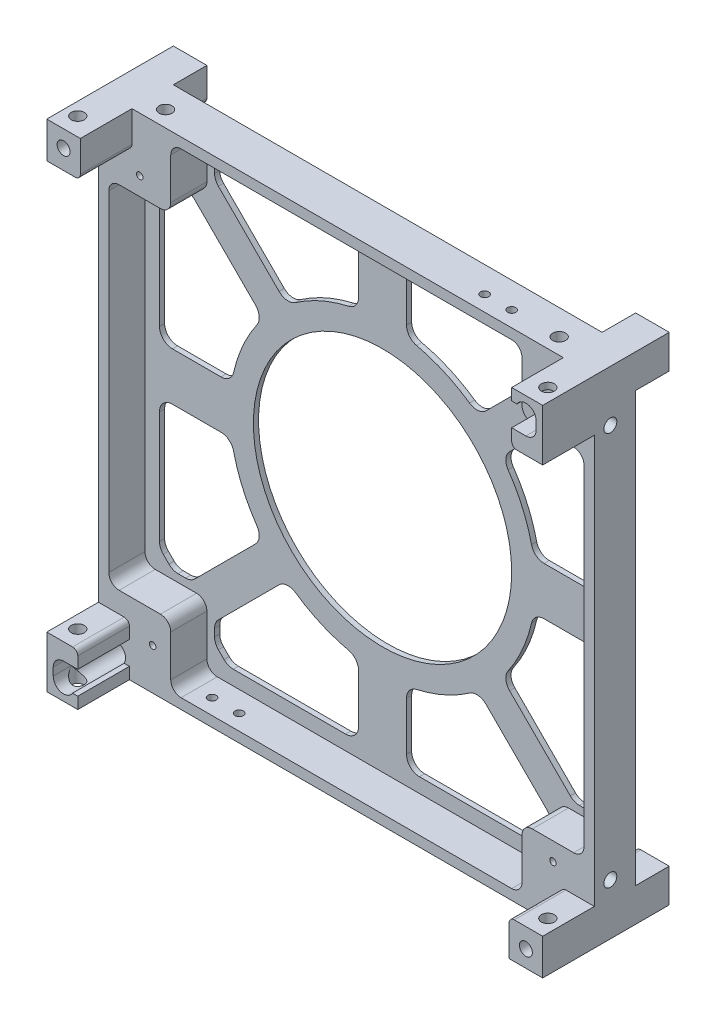
SolidWorks part; units mm, degrees
other "Markup1"
sketch "Sketch35" plane through (-48, 48, 17) normal (-0.4622, 0.8807, 0.1038) x (-0.8777, -0.471, 0.0879)
material "7075-T6 (SN)"
ref_plane "Front Plane" through (0, 0, 0) normal (0, 0, 1) x (1, 0, 0)
ref_plane "Top Plane" through (0, 0, 0) normal (0, 1, 0) x (1, 0, 0)
ref_plane "Right Plane" through (0, 0, 0) normal (1, 0, 0) x (0, 0, -1)
sketch "Sketch1" plane through (0, 0, 0) normal (0, 0, 1) x (1, 0, 0)
  line L0 (0, 0) -> (0, 62.6225) construction
  line L1 (-48, 48) -> (48, 48) construction
  line L2 (-48, 48) -> (-48, -48) construction
  line L3 (-48, -48) -> (48, -48) construction
  line L4 (48, 48) -> (48, -48) construction
  line L5 (0, 0) -> (75.6556, 0) construction
  point P4 (0, 48)
  point P5 (-48, 0)
  dimension "D1" = 96
  dimension "D2" = 96
sketch "Sketch2" plane through (0, 0, 0) normal (0, 0, 1) x (1, 0, 0)
  line L1 (48, 48) -> (41.5, 48)
  line L2 (48, 48) -> (48, 41.5)
  line L3 (48, 41.5) -> (41.5, 41.5)
  line L4 (41.5, 48) -> (41.5, 41.5)
  line L5 (48, -48) -> (41.5, -48)
  line L6 (48, -48) -> (48, -41.5)
  line L7 (48, -41.5) -> (41.5, -41.5)
  line L8 (41.5, -48) -> (41.5, -41.5)
  line L9 (-48, -48) -> (-41.5, -48)
  line L10 (-48, -48) -> (-48, -41.5)
  line L11 (-48, -41.5) -> (-41.5, -41.5)
  line L12 (-41.5, -48) -> (-41.5, -41.5)
  line L13 (-48, 48) -> (-41.5, 48)
  line L14 (-48, 48) -> (-48, 41.5)
  line L15 (-48, 41.5) -> (-41.5, 41.5)
  line L16 (-41.5, 48) -> (-41.5, 41.5)
  dimension "D1" = 6.5
  dimension "D2" = 6.5
  dimension "D3" = 6.5
  dimension "D4" = 6.5
  dimension "D5" = 6.5
  dimension "D6" = 6.5
  dimension "D7" = 6.5
  dimension "D8" = 6.5
sketch "Sketch3" plane through (0, 0, 0) normal (0, 0, 1) x (1, 0, 0)
  line L0 (48, 48) -> (0, 48)
  line L1 (32.5122, 39.5801) -> (32.5122, 38.1157)
  line L3 (38.1157, 32.5122) -> (39.5801, 32.5122)
  line L8 (48, 48) -> (48, -48) construction
  line L9 (48, 0) -> (48, 48)
  line L10 (4.64, 40.68) -> (4.64, 31.2753)
  line L12 (0, 0) -> (48, 48) construction
  line L13 (31.78, 41.3479) -> (30.6801, 42.4478)
  line L14 (25, 0) -> (48, 0)
  line L15 (0, -200000) -> (0, 200062.6225) construction
  line L17 (-48, 48) -> (48, 48) construction
  line L21 (0, 25) -> (0, 48)
  line L22 (20.0352, 24.6032) -> (31.78, 36.3479)
  line L23 (24.6032, 20.0352) -> (36.3479, 31.78)
  line L24 (41.3479, 31.78) -> (42.4478, 30.6801)
  line L25 (7.14, 43.18) -> (28.9124, 43.18)
  line L26 (43.18, 7.14) -> (43.18, 28.9124)
  line L27 (40.68, 4.64) -> (31.2753, 4.64)
  arc A0 (25, 0) -> (0, 25) centre (0, 0) ccw
  arc A1 (28.838, 6.5836) -> (24.3158, 16.8439) centre (0, 0) ccw
  arc A2 (16.8439, 24.3158) -> (6.5836, 28.838) centre (0, 0) ccw
  arc A3 (7.14, 43.18) -> (4.64, 40.68) centre (7.14, 40.68) ccw
  arc A4 (4.64, 31.2753) -> (6.5836, 28.838) centre (7.14, 31.2753) ccw
  arc A5 (20.0352, 24.6032) -> (16.8439, 24.3158) centre (18.2675, 26.3709) cw
  arc A7 (28.9124, 43.18) -> (30.6801, 42.4478) centre (28.9124, 40.68) cw
  arc A8 (31.2753, 4.64) -> (28.838, 6.5836) centre (31.2753, 7.14) cw
  arc A9 (40.68, 4.64) -> (43.18, 7.14) centre (40.68, 7.14) ccw
  arc A10 (43.18, 28.9124) -> (42.4478, 30.6801) centre (40.68, 28.9124) ccw
  arc A11 (24.6032, 20.0352) -> (24.3158, 16.8439) centre (26.3709, 18.2675) ccw
  arc A13 (31.78, 41.3479) -> (32.5122, 39.5801) centre (30.0122, 39.5801) cw
  arc A14 (41.3479, 31.78) -> (39.5801, 32.5122) centre (39.5801, 30.0122) ccw
  arc A15 (36.3479, 31.78) -> (38.1157, 32.5122) centre (38.1157, 30.0122) cw
  arc A16 (31.78, 36.3479) -> (32.5122, 38.1157) centre (30.0122, 38.1157) ccw
  point P39 (4.64, 29.2138)
  point P42 (18.5072, 23.0751)
  point P45 (34.28, 38.8479)
  dimension "D1" = 50
  dimension "D2" = 4.58
  dimension "D10" = 2.5
  dimension "D11" = 2.5
  dimension "D12" = 2.5
  dimension "D13" = 2.5
  dimension "D14" = 2.5
  dimension "D3" = 4.64
  dimension "D4" = 4.82
  dimension "D5" = 6.46
  dimension "D6" = 3.23
  dimension "D7" = 4.82
  dimension "D8" = 4.64
  dimension "D9" = 13.72
extrude "Boss-Extrude2" add sketch "Sketch3" along normal blind 1
ref_axis "Axis1" through (0, 0, 7.875) along (0, 0, -1)
pattern_circular "CirPattern3" count 4 over 360 about axis through (0, 0, 7.875) along (0, 0, -1) of "Boss-Extrude2"
extrude "Boss-Extrude3" add sketch "Sketch2" against normal blind 6.5
sketch "Sketch4" plane through (0, 0, 1) normal (0, 0, 1) x (1, 0, 0)
  line L0 (46, -34) -> (46, 34)
  line L1 (34, 46) -> (-34, 46)
  line L2 (-46, 34) -> (-46, -34)
  line L3 (-34, -46) -> (34, -46)
  line L4 (-48, 48) -> (-48, -48)
  line L5 (-48, -48) -> (48, -48)
  line L6 (48, -48) -> (48, 48)
  line L7 (48, 48) -> (-48, 48)
  line L15 (-46, 34) -> (-34, 34)
  line L16 (-34, 46) -> (-34, 34)
  line L19 (46, 34) -> (34, 34)
  line L20 (34, 46) -> (34, 34)
  line L23 (46, -34) -> (34, -34)
  line L24 (34, -46) -> (34, -34)
  line L27 (-46, -34) -> (-34, -34)
  line L28 (-34, -46) -> (-34, -34)
  line L29 (-34, 46) -> (-46, 34) construction
  point P2 (46, -46)
  point P4 (46, 46)
  point P6 (-46, 46)
  point P7 (-46, -46)
  dimension "D3" = 14
  dimension "D4" = 14
  dimension "D5" = 2
  dimension "D6" = 2
  dimension "D1" = 14
  dimension "D2" = 14
  dimension "D7" = 2
  dimension "D8" = 2
extrude "Boss-Extrude4" add sketch "Sketch4" along normal blind 7
sketch "Sketch5" plane through (0, 0, 8) normal (0, 0, 1) x (1, 0, 0)
  line L1 (-48, 48) -> (-41.5, 48)
  line L2 (-48, 48) -> (-48, 41)
  line L3 (-48, 41) -> (-41.5, 41)
  line L4 (-41.5, 48) -> (-41.5, 41)
  line L5 (48, 48) -> (42, 48)
  line L6 (48, 48) -> (48, 38)
  line L7 (48, 38) -> (42, 38)
  line L8 (42, 48) -> (42, 38)
  line L9 (-48, -48) -> (-42, -48)
  line L10 (-48, -48) -> (-48, -38)
  line L11 (-48, -38) -> (-42, -38)
  line L12 (-42, -48) -> (-42, -38)
  line L13 (48, -48) -> (41.5, -48)
  line L14 (48, -48) -> (48, -41)
  line L15 (48, -41) -> (41.5, -41)
  line L16 (41.5, -48) -> (41.5, -41)
  dimension "D1" = 6.5
  dimension "D2" = 7
  dimension "D3" = 6
  dimension "D4" = 10
  dimension "D5" = 6.5
  dimension "D6" = 7
  dimension "D7" = 10
  dimension "D8" = 6
extrude "Boss-Extrude5" add sketch "Sketch5" along normal blind 10
sketch "RailHolePosition" plane through (0, 48, 0) normal (0, 1, 0) x (1, 0, 0)
  line L0 (45.5, 6.5) -> (45.5, -14.5) construction
  line L1 (48, -18) -> (48, 6.5) construction
  line L5 (-45.5, 6.5) -> (-45.5, -14.5) construction
  line L7 (48, 6.5) -> (41.5, 6.5) construction
  line L8 (-48, -18) -> (-48, 6.5) construction
  line L9 (-41.5, 6.5) -> (-48, 6.5) construction
  dimension "D1" = 21
  dimension "D2" = 2.5
  dimension "D3" = 2.5
hole_wizard "M3 Tapped RailHoles" positions "Sketch12" profile "Sketch13" tap size "M3" standard "ISO"
sketch "Sketch12" plane through (0, 48, 0) normal (0, 1, 0) x (1, 0, 0)
  point P8 (45.5, -14.5)
  point P11 (-45.5, -14.5)
sketch "Sketch13" plane through (45.5, 48, 14.5) normal (1, 0, 0) x (0, 0, 1)
  line L0 (0, 0) -> (0, 13.2511)
  line L1 (0, 13.2511) -> (1.25, 12.5)
  line L2 (1.25, 12.5) -> (1.25, 0)
  line L5 (1.25, 0) -> (0, 0)
  line L10 (0, 13.2511) -> (-1.25, 12.5) construction
  line L11 (0, -6.35) -> (0, 107.95) construction
  dimension "Tap Drill Dia." = 2.5
  dimension "Tap Drill Depth" = 12.5
  dimension "Drill Angle" = 118
cosmetic thread "Hole Thread1" parameters "D1"=7, "D2"=3
cosmetic thread "Hole Thread19" parameters "D1"=7, "D2"=3
sketch3d "SidePlateHole Positions"
  line L0 (-38.1, -48, 8) -> (-38.1, -48, 0) construction
  line L1 (-42, -48, 8) -> (41.5, -48, 8) construction
  line L2 (-48, -48, 0) -> (48, -48, 0) construction
  line L3 (-38.1, -48, 4.9) -> (-48, -48, 4.9) construction
  line L5 (-48, -48, 18) -> (-48, -48, -6.5) construction
  line L6 (-41.5, -48, 0) -> (41.5, -48, 0) construction
  line L17 (-48, -48, 4.9) -> (-48, -38.1, 4.9) construction
  line L18 (-48, -38.1, 4.9) -> (-48, -38.1, 0) construction
  line L19 (-48, 48, 0) -> (-48, -48, 0) construction
  dimension "D1" = 4.9
  dimension "D2" = 9.9
  dimension "D7" = 9.9
hole_wizard "M3x0.5 Tapped SidePlate" positions "Sketch16" profile "Sketch17" tap size "M3x0.5" standard "ANSI Metric"
sketch "Sketch16" plane through (0, -48, 0) normal (0, -1, 0) x (-1, 0, 0)
  point P0 (38.1, -4.9)
sketch "Sketch17" plane through (-38.1, -48, 4.9) normal (1, 0, 0) x (0, 0, -1)
  line L0 (0, 0) -> (0, 8.2511)
  line L1 (0, 8.2511) -> (1.25, 7.5)
  line L2 (1.25, 7.5) -> (1.25, 0)
  line L5 (1.25, 0) -> (0, 0)
  line L10 (0, 8.2511) -> (-1.25, 7.5) construction
  line L11 (0, -6.35) -> (0, 107.95) construction
  dimension "Tap Drill Dia." = 2.5
  dimension "Tap Drill Depth" = 7.5
  dimension "Drill Angle" = 118
cosmetic thread "Hole Thread3" parameters "D1"=6, "D2"=3
hole_wizard "M3x0.5 Tapped SidePlate2" positions "Sketch18" profile "Sketch19" tap size "M3x0.5" standard "ANSI Metric"
sketch "Sketch18" plane through (-48, 0, 0) normal (-1, 0, 0) x (0, 0, 1)
  point P0 (4.9, -38.1)
sketch "Sketch19" plane through (-48, -38.1, 4.9) normal (0, 1, 0) x (0, 0, 1)
  line L0 (0, 0) -> (0, 8.2511)
  line L1 (0, 8.2511) -> (1.25, 7.5)
  line L2 (1.25, 7.5) -> (1.25, 0)
  line L5 (1.25, 0) -> (0, 0)
  line L10 (0, 8.2511) -> (-1.25, 7.5) construction
  line L11 (0, -6.35) -> (0, 107.95) construction
  dimension "Tap Drill Dia." = 2.5
  dimension "Tap Drill Depth" = 7.5
  dimension "Drill Angle" = 118
cosmetic thread "Hole Thread4" parameters "D1"=6, "D2"=3
pattern_circular "SidePlateHoles" count 4 over 360 about axis through (0, 0, 1) along (0, 0, -1) of "M3x0.5 Tapped SidePlate", "M3x0.5 Tapped SidePlate2"
cosmetic thread "Hole Thread5" parameters "D1"=6, "D2"=3
cosmetic thread "Hole Thread6" parameters "D1"=6, "D2"=3
cosmetic thread "Hole Thread7" parameters "D1"=6, "D2"=3
cosmetic thread "Hole Thread8" parameters "D1"=6, "D2"=3
cosmetic thread "Hole Thread9" parameters "D1"=6, "D2"=3
cosmetic thread "Hole Thread10" parameters "D1"=6, "D2"=3
sketch3d "LimitSwitchHolePositions"
  line L0 (-48, -48, 5) -> (-29, -48, 5) construction
  line L1 (-48, -48, 18) -> (-48, -48, -6.5) construction
  line L2 (-48, -48, 0) -> (48, -48, 0) construction
  line L3 (-29, -48, 5) -> (-23.75, -48, 5) construction
  dimension "D1" = 19
  dimension "D2" = 5
  dimension "D3" = 5.25
hole_wizard "M2x0.4 Tapped Hole1" positions "Sketch20" profile "Sketch21" tap size "M2x0.4" standard "ANSI Metric"
sketch "Sketch20" plane through (0, -48, 0) normal (0, -1, 0) x (-1, 0, 0)
  point P0 (29, -5)
  point P3 (23.75, -5)
sketch "Sketch21" plane through (-29, -48, 5) normal (1, 0, 0) x (0, 0, -1)
  line L0 (0, 0) -> (0, 5.6807)
  line L1 (0, 5.6807) -> (0.8, 5.2)
  line L2 (0.8, 5.2) -> (0.8, 0)
  line L5 (0.8, 0) -> (0, 0)
  line L10 (0, 5.6807) -> (-0.8, 5.2) construction
  line L11 (0, -6.35) -> (0, 107.95) construction
  dimension "Tap Drill Dia." = 1.6
  dimension "Tap Drill Depth" = 5.2
  dimension "Drill Angle" = 118
cosmetic thread "Hole Thread11" parameters "D1"=4, "D2"=2
cosmetic thread "Hole Thread12" parameters "D1"=4, "D2"=2
pattern_circular "LimitSwitchHoles" count 2 over 360 about axis through (0, 0, 1) along (0, 0, -1) of "M2x0.4 Tapped Hole1"
cosmetic thread "Hole Thread13" parameters "D1"=4, "D2"=2
cosmetic thread "Hole Thread14" parameters "D1"=4, "D2"=2
fillet "Fillet2" radius 2 12 edges at (-46, -34, 4.5) (-34, -34, 4.5) (-34, -46, 4.5) (34, -46, 4.5) (34, -34, 4.5) (46, -34, 4.5) (46, 34, 4.5) (34, 34, 4.5) (34, 46, 4.5) (-34, 46, 4.5) (-34, 34, 4.5) (-46, 34, 4.5)
sketch "Sketch22" plane through (0, 0, 18) normal (0, 0, 1) x (1, 0, 0)
  line L0 (44.75, 48) -> (44.75, 44.75) construction
  line L1 (48, 48) -> (42, 48) construction
  line L3 (48, 38) -> (48, 48) construction
  dimension "D1" = 3.25
  dimension "D2" = 3.25
hole_wizard "M3 Tapped Standoff Hole" positions "Sketch23" profile "Sketch25" tap size "M3" standard "ISO" end condition through all
sketch "Sketch23" plane through (0, 0, 18) normal (0, 0, 1) x (1, 0, 0)
  point P0 (-44.75, 44.75)
sketch "Sketch25" plane through (-44.75, 44.75, 18) normal (1, 0, 0) x (0, -1, 0)
  line L0 (0, 0) -> (0, 24.5)
  line L1 (0, 24.5) -> (1.25, 24.5)
  line L2 (1.25, 24.5) -> (1.25, 0)
  line L5 (1.25, 0) -> (0, 0)
  line L11 (0, -6.35) -> (0, 107.95) construction
  dimension "Thread Major Dia." = 2.5
  dimension "Thru Tap Drill Depth" = 24.5
pattern_circular "StandoffHoles" count 2 over 360 about axis through (0, 0, 1) along (0, 0, -1) of "M3 Tapped Standoff Hole"
sketch "Sketch26" plane through (0, 0, 0) normal (0, 0, -1) x (-1, 0, 0)
  line L0 (0, 0) -> (37.5, -40) construction
  line L1 (0, -200000) -> (0, 200062.6225) construction
  line L2 (200000, 0) -> (-200075.6556, 0) construction
  line L3 (13.475, 0) -> (-13.475, 0) construction
  line L4 (0, 0) -> (37.5, 40) construction
  circle A0 centre (37.5, -40) radius 1.7
  dimension "D3" = 3.4
  dimension "D1" = 37.5
  dimension "D2" = 40
extrude "Boss-Extrude6" add sketch "Sketch26" along normal blind 3
hole_wizard "CBORE for M5 Hex Head Bolt1" positions "Sketch33" profile "Sketch34" counterbore size "M5" standard "ISO" end condition through all
sketch "Sketch33" plane through (0, 0, 18) normal (0, 0, 1) x (1, 0, 0)
  point P0 (44.75, 44.75)
sketch "Sketch34" plane through (44.75, 44.75, 18) normal (1, 0, 0) x (0, -1, 0)
  line L0 (0, 0) -> (0, 24.5)
  line L1 (0, 24.5) -> (1, 24.5)
  line L3 (1, 24.5) -> (1, 20)
  line L4 (1, 20) -> (2, 20)
  line L5 (2, 20) -> (2, 0)
  line L7 (2, 0) -> (0, 0)
  line L11 (0, -6.35) -> (0, 107.95) construction
  dimension "Thru Hole Dia." = 2
  dimension "Thru Hole Depth" = 24.5
  dimension "C'Bore Dia." = 4
  dimension "C'Bore Depth" = 20
pattern_circular "CirPattern4" count 2 over 360 about axis through (0, 0, 7.875) along (0, 0, -1) of "CBORE for M5 Hex Head Bolt1"
fillet "Fillet3" radius 1 4 edges at (42, 38, 13) (-41.5, 41, 13) (-42, -38, 13) (41.5, -41, 13)
sketch "Sketch36" plane through (0, 0, 8) normal (0, 0, 1) x (1, 0, 0)
  line L0 (-42, -45.75) -> (-43.0179, -45.75)
  line L1 (-42, -48) -> (-42, -39) construction
  line L2 (-42, -48) -> (41.5, -48) construction
  line L3 (-46.75, -44.75) -> (-46.75, -43.25)
  line L4 (-44.75, -41.25) -> (-42, -41.25)
  line L5 (-42, -41.25) -> (-42, -45.75)
  circle A0 centre (-44.75, -44.75) radius 2 construction
  arc A1 (-43.0179, -45.75) -> (-46.75, -44.75) centre (-44.75, -44.75) cw
  arc A2 (-46.75, -43.25) -> (-44.75, -41.25) centre (-44.75, -43.25) cw
  dimension "D2" = 1.5
  dimension "D1" = 2.25
extrude "Cut-Extrude1" cut sketch "Sketch36" along normal up to surface (10 mm away) up to face at (-42.75, -44.75, 18)
pattern_circular "CirPattern5" count 2 over 360 about axis through (0, 0, 7.875) along (0, 0, -1) of "Cut-Extrude1"
pattern_circular "CirPattern6" count 2 over 360 about axis through (0, 0, 7.875) along (0, 0, -1) of "M3 Tapped RailHoles"
cosmetic thread "Hole Thread20" parameters "D1"=7, "D2"=3
cosmetic thread "Hole Thread21" parameters "D1"=7, "D2"=3
fillet "Fillet4" radius 1 4 edges at (-41.5, -41.5, -3.25) (-41.5, 41.5, -3.25) (41.5, 41.5, -3.25) (41.5, -41.5, -3.25)
pattern_circular "CirPattern7" count 4 over 360 about axis through (0, 0, 7.875) along (0, 0, -1) of "Boss-Extrude6"
hole_wizard "Tap Drill for M1.6x0.35 Tap1" positions "3DSketch1" profile "Sketch37" hole size "M1.6x0.35" standard "ANSI Metric" end condition through all
sketch3d "3DSketch1"
  line L0 (-37.5, -40, -3) -> (-37.5, -40, 0) construction
  point P5 (-37.5, -40, -3)
sketch "Sketch37" plane through (-37.5, -40, -3) normal (1, 0, 0) x (0, 1, 0)
  line L0 (0, 0) -> (0, 21)
  line L1 (0, 21) -> (0.625, 21)
  line L2 (0.625, 21) -> (0.625, 0)
  line L5 (0.625, 0) -> (0, 0)
  line L11 (0, -6.35) -> (0, 107.95) construction
  dimension "Thru Hole Dia." = 1.25
  dimension "Thru Hole Depth" = 21
pattern_circular "CirPattern8" count 4 over 360 about axis through (0, 0, 7.875) along (0, 0, -1) of "Tap Drill for M1.6x0.35 Tap1"
